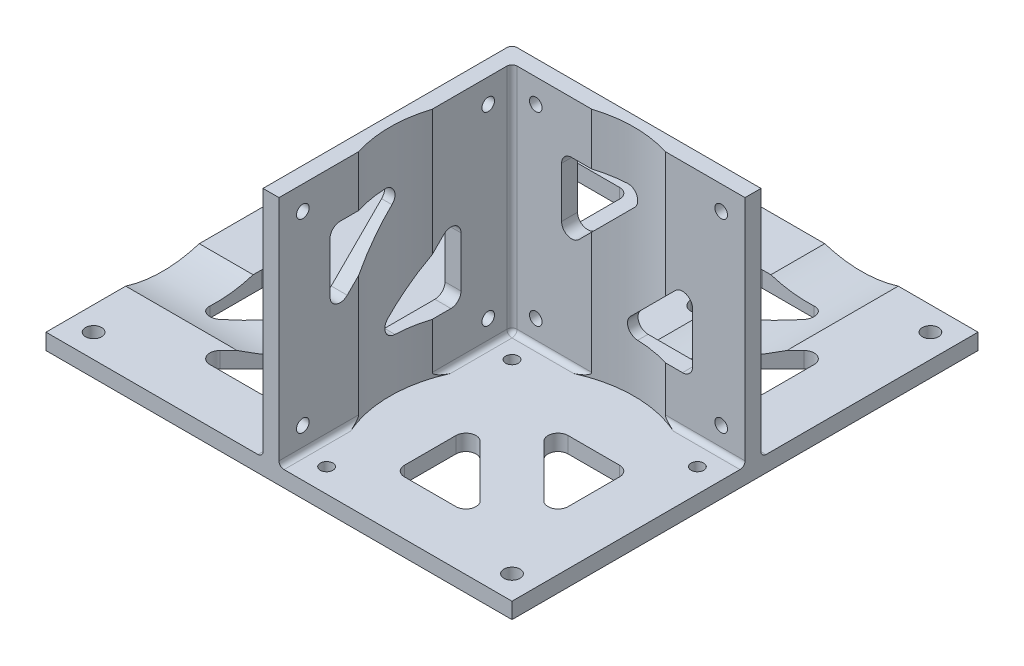
SolidWorks part; units mm, degrees
ref_plane "Front Plane" through (0, 0, 0) normal (0, 0, 1) x (1, 0, 0)
ref_plane "Top Plane" through (0, 0, 0) normal (0, 1, 0) x (1, 0, 0)
ref_plane "Right Plane" through (0, 0, 0) normal (1, 0, 0) x (0, 0, -1)
sketch "Sketch1" plane through (0, 0, 0) normal (0, 1, 0) x (1, 0, 0)
  line L0 (-41.525, 46.25) -> (-41.525, -46.25) construction
  line L1 (-46.25, -46.25) -> (46.25, -46.25)
  line L2 (-46.25, -46.25) -> (-46.25, 46.25)
  line L3 (-46.25, 46.25) -> (46.25, 46.25)
  line L4 (46.25, -46.25) -> (46.25, 46.25)
  line L5 (-46.25, -46.25) -> (46.25, 46.25) construction
  line L6 (-46.25, 46.25) -> (46.25, -46.25) construction
  line L7 (-46.25, -41.525) -> (46.25, -41.525) construction
  line L8 (41.525, -46.25) -> (41.525, 46.25) construction
  line L9 (-46.25, 41.525) -> (46.25, 41.525) construction
  circle A0 centre (-41.525, -41.525) radius 1.6
  circle A1 centre (-41.525, 41.525) radius 1.6
  circle A2 centre (41.525, 41.525) radius 1.6
  circle A3 centre (41.525, -41.525) radius 1.6
  point P0 (0, 0)
  dimension "D7" = 3.2
  dimension "D8" = 3.2
  dimension "D9" = 3.2
  dimension "D10" = 3.2
  dimension "D1" = 92.5
  dimension "D2" = 92.5
  dimension "D3" = 4.725
  dimension "D4" = 4.725
  dimension "D5" = 4.725
  dimension "D6" = 4.725
extrude "Base Plate" add sketch "Sketch1" along normal blind 3.175
sketch "Sketch2" plane through (0, 3.175, 0) normal (0, 1, 0) x (1, 0, 0)
  line L0 (0, 0) -> (46.25, 0)
  line L1 (46.25, -46.25) -> (46.25, 46.25) construction
  line L2 (0, 0) -> (0, -46.25)
  line L3 (-46.25, -46.25) -> (46.25, -46.25) construction
  line L4 (-3.175, -46.25) -> (-3.175, 3.175)
  line L7 (-3.175, 3.175) -> (46.25, 3.175)
  line L8 (-3.175, -46.25) -> (0, -46.25)
  line L9 (46.25, 0) -> (46.25, 3.175)
  dimension "D1" = 46.25
  dimension "D2" = 3.175
  dimension "D3" = 3.175
extrude "L-Bracket" add sketch "Sketch2" along normal blind 46.25
sketch "Sketch3" plane through (0, 3.175, 0) normal (0, 1, 0) x (1, 0, 0)
  line L0 (0, 0) -> (46.25, -46.25) construction
  line L1 (0, -46.25) -> (46.25, 0) construction
  line L5 (0, -46.25) -> (0, 0) construction
  circle A0 centre (23.125, -23.125) radius 21.625 construction
  circle A2 centre (41.525, -4.725) radius 0.2
  circle A3 centre (4.725, -4.725) radius 0.2
  circle A4 centre (4.725, -41.525) radius 0.2
  dimension "D1" = 43.25
  dimension "D4" = 4.725
extrude "RW Holes" cut sketch "Sketch3" against normal through all
sketch "Sketch7" plane through (0, 0, 0) normal (0, 0, 1) x (1, 0, 0)
  line L0 (0, 3.175) -> (46.25, 49.425) construction
  line L1 (0, 49.425) -> (46.25, 3.175) construction
  line L2 (46.25, 49.425) -> (46.25, 3.175) construction
  line L3 (0, 3.175) -> (46.25, 3.175) construction
  circle A0 centre (23.125, 26.3) radius 21.625 construction
  circle A1 centre (41.525, 7.9) radius 0.2
  circle A2 centre (4.725, 7.9) radius 0.2
  circle A3 centre (4.725, 44.7) radius 0.2
  circle A4 centre (41.525, 44.7) radius 0.2
  dimension "D1" = 43.25
  dimension "D2" = 0.4
  dimension "D3" = 4
  dimension "D4" = 4.725
  dimension "D5" = 41.525
  dimension "D6" = 4.725
  dimension "D8" = 46.25
extrude "RW Holes 2" cut sketch "Sketch7" against normal through all
sketch "Sketch8" plane through (0, 0, 0) normal (1, 0, 0) x (0, 0, -1)
  line L0 (-46.25, 49.425) -> (0, 3.175) construction
  line L1 (-46.25, 3.175) -> (0, 49.425) construction
  line L2 (-46.25, 3.175) -> (0, 3.175) construction
  circle A0 centre (-23.125, 26.3) radius 21.625 construction
  circle A1 centre (-41.525, 7.9) radius 0.2
  circle A2 centre (-41.525, 44.7) radius 0.2
  circle A3 centre (-4.725, 44.7) radius 0.2
  circle A4 centre (-4.725, 7.9) radius 0.2
  dimension "D1" = 43.25
  dimension "D4" = 0.4
  dimension "D2" = 4
  dimension "D3" = 4.725
  dimension "D5" = 41.525
  dimension "D6" = 4.725
extrude "RW Holes 3" cut sketch "Sketch8" against normal blind 45
sketch "Sketch10" plane through (0, 0, 0) normal (0, -1, 0) x (1, 0, 0)
  line L0 (-46.25, 46.25) -> (46.25, -46.25) construction
  line L1 (21.9291, 15.6133) -> (32.1447, 25.8289)
  line L2 (-46.25, -46.25) -> (46.25, 46.25) construction
  line L3 (35.559, 24.4147) -> (35.559, 14.1991)
  line L4 (33.559, 12.1991) -> (23.3433, 12.1991)
  line L5 (46.25, 46.25) -> (46.25, -46.25) construction
  line L6 (24.4147, 35.559) -> (14.1991, 35.559)
  line L7 (15.6133, 21.9291) -> (25.8289, 32.1447)
  line L8 (12.1991, 33.559) -> (12.1991, 23.3433)
  line L9 (35.559, -24.4147) -> (35.559, -14.1991)
  line L10 (33.559, -12.1991) -> (23.3433, -12.1991)
  line L11 (21.9291, -15.6133) -> (32.1447, -25.8289)
  line L12 (12.1991, -33.559) -> (12.1991, -23.3433)
  line L13 (15.6133, -21.9291) -> (25.8289, -32.1447)
  line L14 (24.4147, -35.559) -> (14.1991, -35.559)
  line L15 (-24.4147, -35.559) -> (-14.1991, -35.559)
  line L16 (-12.1991, -33.559) -> (-12.1991, -23.3433)
  line L17 (-15.6133, -21.9291) -> (-25.8289, -32.1447)
  line L18 (-33.559, -12.1991) -> (-23.3433, -12.1991)
  line L19 (-21.9291, -15.6133) -> (-32.1447, -25.8289)
  line L20 (-35.559, -24.4147) -> (-35.559, -14.1991)
  line L21 (-35.559, 24.4147) -> (-35.559, 14.1991)
  line L22 (-33.559, 12.1991) -> (-23.3433, 12.1991)
  line L23 (-21.9291, 15.6133) -> (-32.1447, 25.8289)
  line L24 (-12.1991, 33.559) -> (-12.1991, 23.3433)
  line L25 (-15.6133, 21.9291) -> (-25.8289, 32.1447)
  line L26 (-24.4147, 35.559) -> (-14.1991, 35.559)
  arc A0 (35.559, 14.1991) -> (33.559, 12.1991) centre (33.559, 14.1991) cw
  arc A1 (32.1447, 25.8289) -> (35.559, 24.4147) centre (33.559, 24.4147) cw
  arc A2 (21.9291, 15.6133) -> (23.3433, 12.1991) centre (23.3433, 14.1991) ccw
  arc A3 (25.8289, 32.1447) -> (24.4147, 35.559) centre (24.4147, 33.559) ccw
  arc A4 (14.1991, 35.559) -> (12.1991, 33.559) centre (14.1991, 33.559) ccw
  arc A5 (15.6133, 21.9291) -> (12.1991, 23.3433) centre (14.1991, 23.3433) cw
  arc A6 (35.559, -14.1991) -> (33.559, -12.1991) centre (33.559, -14.1991) ccw
  arc A7 (21.9291, -15.6133) -> (23.3433, -12.1991) centre (23.3433, -14.1991) cw
  arc A8 (32.1447, -25.8289) -> (35.559, -24.4147) centre (33.559, -24.4147) ccw
  arc A9 (15.6133, -21.9291) -> (12.1991, -23.3433) centre (14.1991, -23.3433) ccw
  arc A10 (14.1991, -35.559) -> (12.1991, -33.559) centre (14.1991, -33.559) cw
  arc A11 (25.8289, -32.1447) -> (24.4147, -35.559) centre (24.4147, -33.559) cw
  arc A12 (-14.1991, -35.559) -> (-12.1991, -33.559) centre (-14.1991, -33.559) ccw
  arc A13 (-15.6133, -21.9291) -> (-12.1991, -23.3433) centre (-14.1991, -23.3433) cw
  arc A14 (-25.8289, -32.1447) -> (-24.4147, -35.559) centre (-24.4147, -33.559) ccw
  arc A15 (-21.9291, -15.6133) -> (-23.3433, -12.1991) centre (-23.3433, -14.1991) ccw
  arc A16 (-35.559, -14.1991) -> (-33.559, -12.1991) centre (-33.559, -14.1991) cw
  arc A17 (-32.1447, -25.8289) -> (-35.559, -24.4147) centre (-33.559, -24.4147) cw
  arc A18 (-35.559, 14.1991) -> (-33.559, 12.1991) centre (-33.559, 14.1991) ccw
  arc A19 (-21.9291, 15.6133) -> (-23.3433, 12.1991) centre (-23.3433, 14.1991) cw
  arc A20 (-32.1447, 25.8289) -> (-35.559, 24.4147) centre (-33.559, 24.4147) ccw
  arc A21 (-15.6133, 21.9291) -> (-12.1991, 23.3433) centre (-14.1991, 23.3433) ccw
  arc A22 (-14.1991, 35.559) -> (-12.1991, 33.559) centre (-14.1991, 33.559) cw
  arc A23 (-25.8289, 32.1447) -> (-24.4147, 35.559) centre (-24.4147, 33.559) cw
  point P18 (35.559, 29.2431)
  point P21 (18.5149, 12.1991)
  dimension "D4" = 2
  dimension "D1" = 10.691
  dimension "D2" = 27.7351
  dimension "D3" = 17.0069
  dimension "D6" = 10.691
  dimension "D7" = 58.4491
  dimension "D5" = 4
extrude "WR1" cut sketch "Sketch10" against normal blind 45
sketch "Sketch11" plane through (0, 0, 0) normal (1, 0, 0) x (0, 0, -1)
  line L0 (-46.25, 49.425) -> (0, 3.175) construction
  line L1 (-46.25, 3.175) -> (0, 49.425) construction
  line L2 (-36.1242, 37.2992) -> (-36.1242, 27.2939)
  line L3 (-32.71, 25.8797) -> (-22.7047, 35.885)
  line L4 (-34.1242, 39.2992) -> (-24.1189, 39.2992)
  line L5 (-10.1258, 15.3008) -> (-10.1258, 25.3061)
  line L6 (-23.5453, 16.715) -> (-13.54, 26.7203)
  line L7 (-12.1258, 13.3008) -> (-22.1311, 13.3008)
  circle A0 centre (-4.725, 44.7) radius 0.2 construction
  arc A1 (-22.7047, 35.885) -> (-24.1189, 39.2992) centre (-24.1189, 37.2992) ccw
  arc A2 (-36.1242, 37.2992) -> (-34.1242, 39.2992) centre (-34.1242, 37.2992) cw
  arc A3 (-36.1242, 27.2939) -> (-32.71, 25.8797) centre (-34.1242, 27.2939) ccw
  arc A4 (-13.54, 26.7203) -> (-10.1258, 25.3061) centre (-12.1258, 25.3061) cw
  arc A5 (-12.1258, 13.3008) -> (-10.1258, 15.3008) centre (-12.1258, 15.3008) ccw
  arc A6 (-22.1311, 13.3008) -> (-23.5453, 16.715) centre (-22.1311, 15.3008) cw
  point P19 (-19.2905, 39.2992)
  point P22 (-36.1242, 39.2992)
  point P25 (-36.1242, 22.4655)
  dimension "D3" = 2
  dimension "D1" = 16.8337
  dimension "D2" = 14.5655
extrude "WR2" cut sketch "Sketch11" against normal blind 10
sketch "Sketch12" plane through (0, 0, 0) normal (0, 0, 1) x (1, 0, 0)
  line L0 (-0.2859, 49.2555) -> (45.9641, 3.0055) construction
  line L1 (-0.2859, 3.0055) -> (45.9641, 49.2555) construction
  line L2 (9.8399, 37.1297) -> (9.8399, 27.1244)
  line L3 (13.2541, 25.7102) -> (23.2594, 35.7154)
  line L4 (11.8399, 39.1297) -> (21.8451, 39.1297)
  line L5 (35.8382, 15.1313) -> (35.8382, 25.1365)
  line L6 (22.4188, 16.5455) -> (32.424, 26.5508)
  line L7 (33.8382, 13.1313) -> (23.833, 13.1313)
  arc A1 (23.2594, 35.7154) -> (21.8451, 39.1297) centre (21.8451, 37.1297) ccw
  arc A2 (9.8399, 37.1297) -> (11.8399, 39.1297) centre (11.8399, 37.1297) cw
  arc A3 (9.8399, 27.1244) -> (13.2541, 25.7102) centre (11.8399, 27.1244) ccw
  arc A4 (32.424, 26.5508) -> (35.8382, 25.1365) centre (33.8382, 25.1365) cw
  arc A5 (33.8382, 13.1313) -> (35.8382, 15.1313) centre (33.8382, 15.1313) ccw
  arc A6 (23.833, 13.1313) -> (22.4188, 16.5455) centre (23.833, 15.1313) cw
  circle A7 centre (4.725, 44.7) radius 0.2 construction
  point P19 (26.6736, 39.1297)
  point P22 (9.8399, 39.1297)
  point P25 (9.8399, 22.296)
  dimension "D3" = 2
  dimension "D1" = 16.8337
  dimension "D2" = 5.1149
  dimension "D4" = 17.6938
  dimension "D5" = 41.2391
  dimension "D6" = 4.5555
extrude "WR3" cut sketch "Sketch12" against normal blind 10
fillet "Fillet1" radius 1 6 edges at (0, 26.3, 0) (23.125, 3.175, 0) (0, 3.175, 23.125) (-3.175, 26.3, -3.175) (21.5375, 3.175, -3.175) (-3.175, 3.175, 21.5375)
hole_wizard "Tap Drill for M3x0.5 Tap1" positions "3DSketch2" profile "Sketch14" hole size "M3x0.5" standard "ANSI Metric" end condition through all
sketch3d "3DSketch2"
  line L0 (41.525, 0, 4.725) -> (41.525, 3.175, 4.725) construction
  line L1 (4.725, 0, 4.725) -> (4.725, 3.175, 4.725) construction
  line L2 (4.725, 0, 41.525) -> (4.725, 3.175, 41.525) construction
  point P0 (41.525, 3.175, 4.725)
  point P4 (4.725, 3.175, 4.725)
  point P8 (4.725, 3.175, 41.525)
sketch "Sketch14" plane through (41.525, 3.175, 4.725) normal (1, 0, 0) x (0, 0, 1)
  line L0 (0, 0) -> (0, 3.175)
  line L1 (0, 3.175) -> (1.25, 3.175)
  line L2 (1.25, 3.175) -> (1.25, 0)
  line L5 (1.25, 0) -> (0, 0)
  line L11 (0, -6.35) -> (0, 107.95) construction
  dimension "Thru Hole Dia." = 2.5
  dimension "Thru Hole Depth" = 3.175
hole_wizard "Tap Drill for M3x0.5 Tap2" positions "3DSketch3" profile "Sketch15" hole size "M3x0.5" standard "ANSI Metric" end condition through all
sketch3d "3DSketch3"
  line L0 (41.525, 44.7, -3.175) -> (41.525, 44.7, 0) construction
  line L1 (41.525, 7.9, -3.175) -> (41.525, 7.9, 0) construction
  line L2 (4.725, 7.9, -3.175) -> (4.725, 7.9, 0) construction
  line L3 (4.725, 44.7, -3.175) -> (4.725, 44.7, 0) construction
  point P0 (41.525, 44.7, 0)
  point P4 (41.525, 7.9, 0)
  point P8 (4.725, 7.9, 0)
  point P12 (4.725, 44.7, 0)
sketch "Sketch15" plane through (41.525, 44.7, 0) normal (1, 0, 0) x (0, -1, 0)
  line L0 (0, 0) -> (0, 46.25)
  line L1 (0, 46.25) -> (1.25, 46.25)
  line L2 (1.25, 46.25) -> (1.25, 0)
  line L5 (1.25, 0) -> (0, 0)
  line L11 (0, -6.35) -> (0, 107.95) construction
  dimension "Thru Hole Dia." = 2.5
  dimension "Thru Hole Depth" = 46.25
hole_wizard "Tap Drill for M3x0.5 Tap3" positions "3DSketch4" profile "Sketch16" hole size "M3x0.5" standard "ANSI Metric" end condition through all
sketch3d "3DSketch4"
  line L0 (-3.175, 44.7, 4.725) -> (0, 44.7, 4.725) construction
  line L1 (-3.175, 44.7, 41.525) -> (0, 44.7, 41.525) construction
  line L2 (-3.175, 7.9, 41.525) -> (0, 7.9, 41.525) construction
  line L3 (-3.175, 7.9, 4.725) -> (0, 7.9, 4.725) construction
  point P0 (-3.175, 44.7, 4.725)
  point P4 (-3.175, 44.7, 41.525)
  point P8 (-3.175, 7.9, 41.525)
  point P12 (-3.175, 7.9, 4.725)
sketch "Sketch16" plane through (-3.175, 44.7, 4.725) normal (0, 1, 0) x (0, 0, 1)
  line L0 (0, 0) -> (0, 49.425)
  line L1 (0, 49.425) -> (1.25, 49.425)
  line L2 (1.25, 49.425) -> (1.25, 0)
  line L5 (1.25, 0) -> (0, 0)
  line L11 (0, -6.35) -> (0, 107.95) construction
  dimension "Thru Hole Dia." = 2.5
  dimension "Thru Hole Depth" = 49.425
sketch "Sketch18" plane through (0, 49.425, 0) normal (0, 1, 0) x (1, 0, 0)
  line L0 (41.525, -41.525) -> (4.725, -4.725) construction
  line L1 (41.525, -4.725) -> (4.725, -41.525) construction
  circle A0 centre (23.125, -23.125) radius 24.25
extrude "Cut-Extrude1" cut sketch "Sketch18" against normal up to surface (46.25 mm away) up to face at (41.525, 3.175, 5.975)
sketch "Sketch19" plane through (0, 0, -46.25) normal (0, 0, -1) x (-1, 0, 0)
  line L0 (-41.525, 44.7) -> (-4.725, 7.9) construction
  line L1 (-4.725, 44.7) -> (-41.525, 7.9) construction
  circle A0 centre (-23.125, 26.3) radius 24.25
extrude "Cut-Extrude2" cut sketch "Sketch19" against normal up to surface (43.075 mm away) contours A0 up to face at (42.775, 44.7, -3.175)
sketch "Sketch20" plane through (-46.25, 0, 0) normal (-1, 0, 0) x (0, 0, 1)
  line L0 (4.725, 44.7) -> (41.525, 7.9) construction
  line L1 (41.525, 44.7) -> (4.725, 7.9) construction
  circle A0 centre (23.125, 26.3) radius 24.25
extrude "Cut-Extrude3" cut sketch "Sketch20" against normal up to surface (43.075 mm away) up to face at (-3.175, 44.7, 5.975)
sketch "Sketch21" plane through (0, 0, 0) normal (0, -1, 0) x (1, 0, 0)
  line L0 (46.25, -46.25) -> (-46.25, 46.25) construction
  line L1 (-46.25, -46.25) -> (46.25, 46.25) construction
  circle A0 centre (0, 0) radius 3.3204
